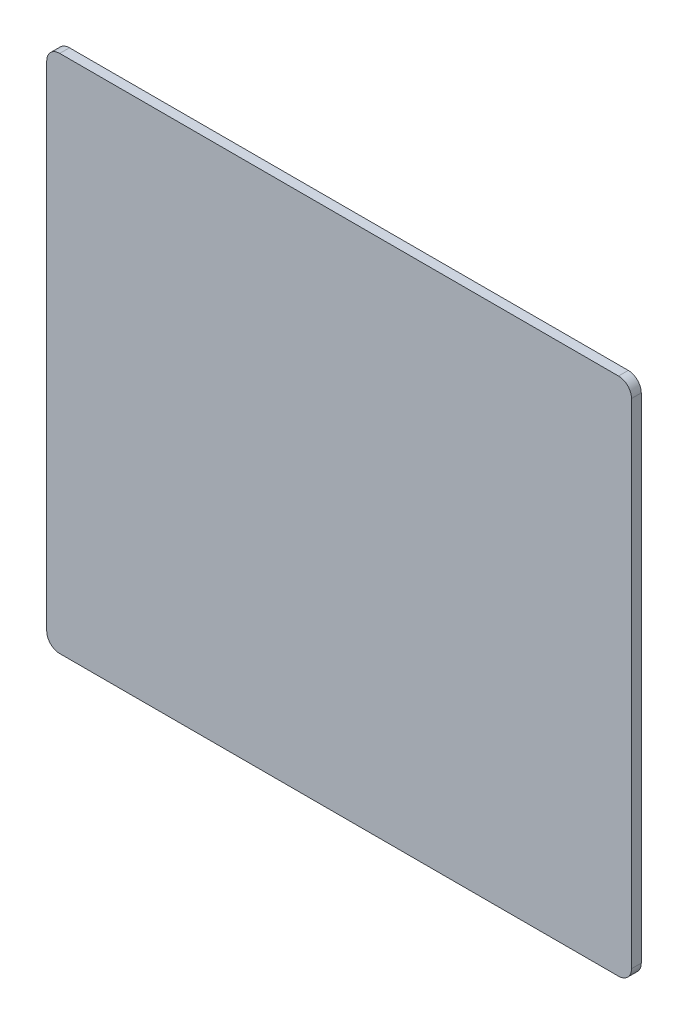
SolidWorks part; units mm, degrees
ref_plane "Спереди" through (0, 0, 0) normal (0, 0, 1) x (1, 0, 0)
ref_plane "Сверху" through (0, 0, 0) normal (0, 1, 0) x (1, 0, 0)
ref_plane "Справа" through (0, 0, 0) normal (1, 0, 0) x (0, 0, -1)
sketch "Эскиз1" plane through (0, 0, 0) normal (0, 0, 1) x (1, 0, 0)
  line L1 (51.5, 19.1073) -> (-34.5, 19.1073)
  line L2 (53.5, 17.1073) -> (53.5, -58.8927)
  line L3 (51.5, -60.8927) -> (-34.5, -60.8927)
  line L4 (-36.5, 17.1073) -> (-36.5, -58.8927)
  line L5 (53.5, 19.1073) -> (-36.5, -60.8927) construction
  line L6 (53.5, -60.8927) -> (-36.5, 19.1073) construction
  arc A0 (51.5, 19.1073) -> (53.5, 17.1073) centre (51.5, 17.1073) cw
  arc A1 (53.5, -58.8927) -> (51.5, -60.8927) centre (51.5, -58.8927) cw
  arc A2 (-34.5, -60.8927) -> (-36.5, -58.8927) centre (-34.5, -58.8927) cw
  arc A3 (-34.5, 19.1073) -> (-36.5, 17.1073) centre (-34.5, 17.1073) ccw
  point P0 (8.5, -20.8927)
  dimension "D3" = 2
  dimension "D1" = 90
  dimension "D2" = 80
base flange "Базовая кромка1" sketch "Эскиз1" thickness 1.5 reverse thickness direction no parameters "D1"=3
sketch "Сгиб-Линии1" [suppressed] plane through (0, 0, 0) normal (0, 1, 0) x (1, 0, 0)
sketch "Граничная рамка1" [suppressed] plane through (0, 0, 0) normal (0, 1, 0) x (1, 0, 0)
sheet metal parameters "Листовой металл1" thickness 1.5 parameters "D1"=3
flat pattern "Развертка1" [suppressed]
sketch "Сгиб-Линии2" plane through (0, 0, 0) normal (0, 1, 0) x (1, 0, 0)
sketch3d "Граничная рамка2" [suppressed]
  line L0 (-88, 2, 0) -> (2, 2, 0) construction
  line L1 (-88, -78, 0) -> (2, -78, 0) construction
  line L2 (-88, 2, 0) -> (-88, -78, 0) construction
  line L3 (2, 2, 0) -> (2, -78, 0) construction
